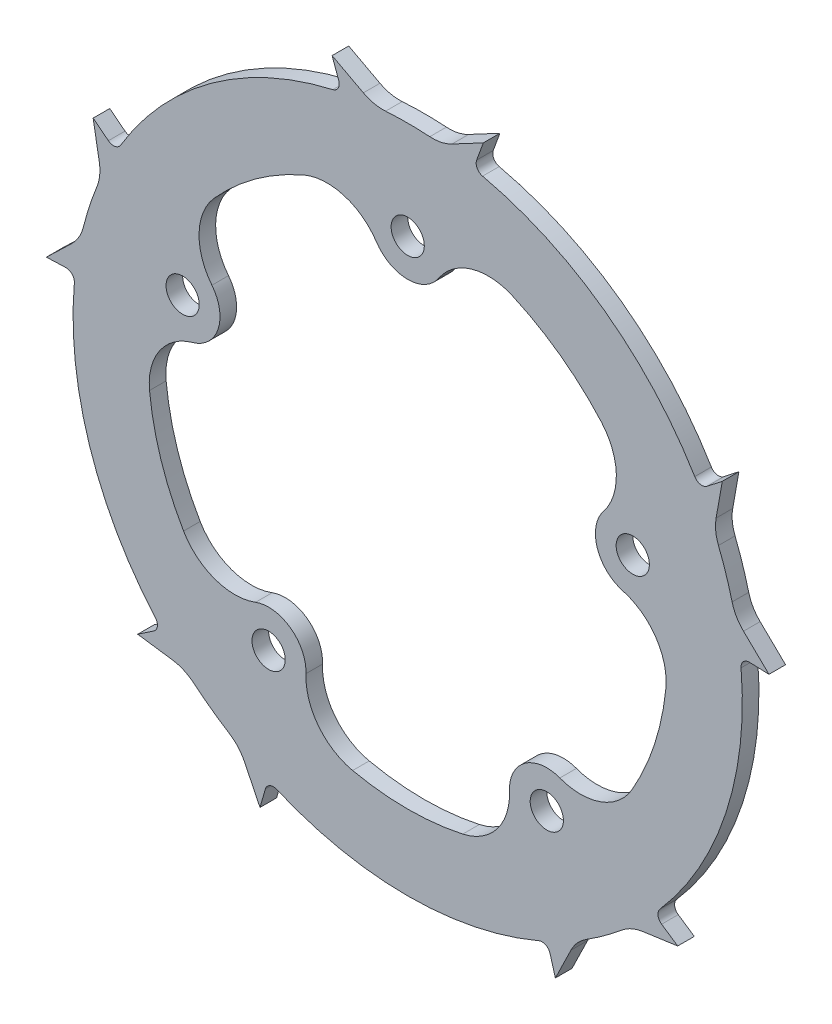
SolidWorks part; units mm, degrees
material "Alloy Steel (SS)"
ref_plane "Front Plane" through (0, 0, 0) normal (0, 0, 1) x (1, 0, 0)
ref_plane "Top Plane" through (0, 0, 0) normal (0, 1, 0) x (1, 0, 0)
ref_plane "Right Plane" through (0, 0, 0) normal (1, 0, 0) x (0, 0, -1)
sketch "Sketch1" plane through (0, 0, 0) normal (0, 0, 1) x (1, 0, 0)
  line L0 (0, 0) -> (0, 28.956) construction
  line L1 (0, 0) -> (27.5388, 8.9479) construction
  line L2 (0, 0) -> (17.0199, -23.4259) construction
  line L3 (0, 0) -> (-17.0199, -23.4259) construction
  line L4 (0, 0) -> (-27.5388, 8.9479) construction
  line L5 (-8.0395, 40.1531) -> (-9.25, 43.4769)
  line L6 (-9.25, 43.4769) -> (0, 0) construction
  line L7 (-9.25, 43.4769) -> (-5.4243, 41.4437)
  line L8 (0, 0) -> (0, 44.45) construction
  line L9 (8.0395, 40.1531) -> (9.25, 43.4769)
  line L10 (9.25, 43.4769) -> (5.4243, 41.4437)
  line L11 (-8.5217, 40.0535) -> (15.957, 45.2615) construction
  line L12 (-9.25, 43.4769) -> (-2.443, 44.9251) construction
  circle A0 centre (0, 0) radius 44.45 construction
  circle A1 centre (0, 0) radius 31.75
  circle A2 centre (0, 28.956) radius 2.032
  arc A3 (3.81, 26.4287) -> (-3.81, 26.4287) centre (0, 28.956) cw
  arc A4 (3.81, 26.4287) -> (12.7862, 29.0616) centre (9.8617, 22.4145) cw
  arc A5 (-3.81, 26.4287) -> (-12.7862, 29.0616) centre (-9.8617, 22.4145) ccw
  arc A6 (23.9579, 11.7905) -> (23.6881, 21.1409) centre (18.2701, 16.3055) ccw
  arc A7 (26.3126, 4.5434) -> (23.9579, 11.7905) centre (27.5388, 8.9479) cw
  circle A8 centre (27.5388, 8.9479) radius 2.032
  arc A9 (26.3126, 4.5434) -> (31.5904, -3.1798) centre (24.3649, -2.4525) cw
  arc A10 (18.6168, -19.1418) -> (27.4262, -15.9958) centre (21.1532, -12.3372) ccw
  arc A11 (12.4521, -23.6208) -> (18.6168, -19.1418) centre (17.0199, -23.4259) cw
  circle A12 centre (17.0199, -23.4259) radius 2.032
  arc A13 (12.4521, -23.6208) -> (6.7378, -31.0268) centre (5.1967, -23.9303) cw
  arc A14 (-12.4521, -23.6208) -> (-6.7378, -31.0268) centre (-5.1967, -23.9303) ccw
  arc A15 (-18.6168, -19.1418) -> (-12.4521, -23.6208) centre (-17.0199, -23.4259) cw
  circle A16 centre (-17.0199, -23.4259) radius 2.032
  arc A17 (-18.6168, -19.1418) -> (-27.4262, -15.9958) centre (-21.1532, -12.3372) cw
  arc A18 (-26.3126, 4.5434) -> (-31.5904, -3.1798) centre (-24.3649, -2.4525) ccw
  arc A19 (-23.9579, 11.7905) -> (-26.3126, 4.5434) centre (-27.5388, 8.9479) cw
  circle A20 centre (-27.5388, 8.9479) radius 2.032
  arc A21 (-23.9579, 11.7905) -> (-23.6881, 21.1409) centre (-18.2701, 16.3055) cw
  circle A22 centre (0, 0) radius 40.95
  arc A23 (-5.4243, 41.4437) -> (-2.7047, 40.8606) centre (-3.0402, 45.9295) ccw
  arc A24 (5.4243, 41.4437) -> (2.7047, 40.8606) centre (3.0402, 45.9295) cw
  point P47 (0, 0)
  dimension "D1" = 88.9
  dimension "D2" = 63.5
  dimension "D3" = 4.064
  dimension "D4" = 28.956
  dimension "D6" = 2.54
  dimension "D8" = 3.5
  dimension "D12" = 5.08
  dimension "D10" = 40
  dimension "D7" = 7.62
  dimension "D9" = 8
  dimension "D11" = 18.5
  dimension "D5" = 5
extrude "Boss-Extrude1" add sketch "Sketch1" along normal blind 2.032 contours A0 A1 | A19 A21 A1 A18 A20 | A5 A3 A4 A1 A2 | A7 A9 A1 A6 A8 | A11 A13 A1 A10 A12 | A15 A17 A1 A14 A16 region at (-5.2315, 39.4464, 0) region at (31.6842, -1.5906, 0) region at (7.7428, 29.6383, 0) region at (18.5119, -25.4794, 0) region at (-25.7875, 16.5223, 0) region at (-18.5119, -25.4794, 0)
extrude "Boss-Extrude5" add sketch "Sketch1<5>" along normal up to surface (2.032 mm away) contours L7 L5 A22 | A22 L9 L10 region at (-7.0639, 41.4603, 0) region at (7.0639, 41.4603, 0) up to face at (0, 0, 2.032)
sketch "Sketch1<5>" plane through (0, 0, 0) normal (0, 0, 1) x (1, 0, 0) same geometry as "Sketch1"
fillet "Fillet2" radius 1.016 2 edges at (8.0395, 40.1531, 1.016) (-8.0395, 40.1531, 1.016)
pattern_circular "CirPattern2" count 5 over 360 about axis through (0, 0, 2.032) along (0, 0, 1) of "Boss-Extrude5", "Fillet2"
